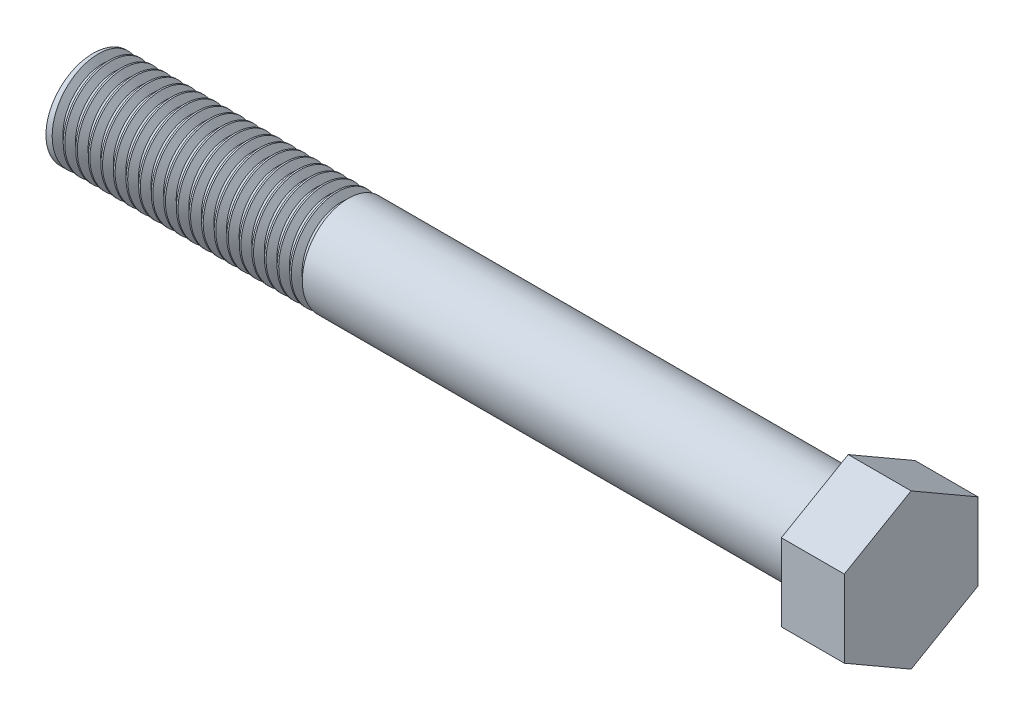
SolidWorks part; units mm, degrees
ref_plane "Front Plane" through (0, 0, 0) normal (0, 0, 1) x (1, 0, 0)
ref_plane "Top Plane" through (0, 0, 0) normal (0, 1, 0) x (1, 0, 0)
ref_plane "Right Plane" through (0, 0, 0) normal (1, 0, 0) x (0, 0, -1)
sketch "Sketch1" plane through (0, 0, 0) normal (1, 0, 0) x (0, 0, -1)
  line L0 (-13.4938, 0) -> (0, 0) construction
  line L1 (-13.4938, 7.7906) -> (-13.4937, -7.7906)
  line L2 (-13.4937, -7.7906) -> (0, -15.5812)
  line L3 (0, -15.5812) -> (13.4937, -7.7906)
  line L4 (13.4937, -7.7906) -> (13.4937, 7.7906)
  line L5 (13.4937, 7.7906) -> (0, 15.5812)
  line L6 (0, 15.5812) -> (-13.4938, 7.7906)
  circle A0 centre (0, 0) radius 13.4938 construction
  dimension "D1" = 26.9875
extrude "Boss-Extrude1" add sketch "Sketch1" along normal blind 12.7
sketch "Sketch2" plane through (0, 0, 0) normal (-1, 0, 0) x (0, 0, 1)
  circle A0 centre (0, 0) radius 9.525
  dimension "D1" = 19.05
extrude "Boss-Extrude2" add sketch "Sketch2" along normal blind 152.4
thread "Thread1" pitch 2.54 method cut profile "Thread Profile1" start angle 0, offset 0, length 50.8, pitch 2.54, diameter 19.05
ref_plane "Plane1" through (-152.4, 0, -9.525) normal (0, -1, 0) x (0, 0, -1)
sketch "Thread Profile1" plane through (-152.4, 0, -9.525) normal (0, -1, 0) x (0, 0, -1)
  line L0 (0, 0) -> (0, 2.54) construction
  line L11 (0, 0) -> (0, 2.2225)
  line L12 (0, 2.2225) -> (-1.3748, 1.4287)
  line L13 (-1.3748, 1.4287) -> (-1.3748, 0.7937)
  line L15 (-1.3748, 0.7937) -> (0, 0)
  line L17 (-1.3748, 1.1112) -> (0, 1.1112) construction
  point P2 (0, 0)
  dimension "Pitch" = 2.54
  dimension "Profile_Angle" = 60
  dimension "Profile_Land" = 0.635
  dimension "Profile_Height" = 1.3748
